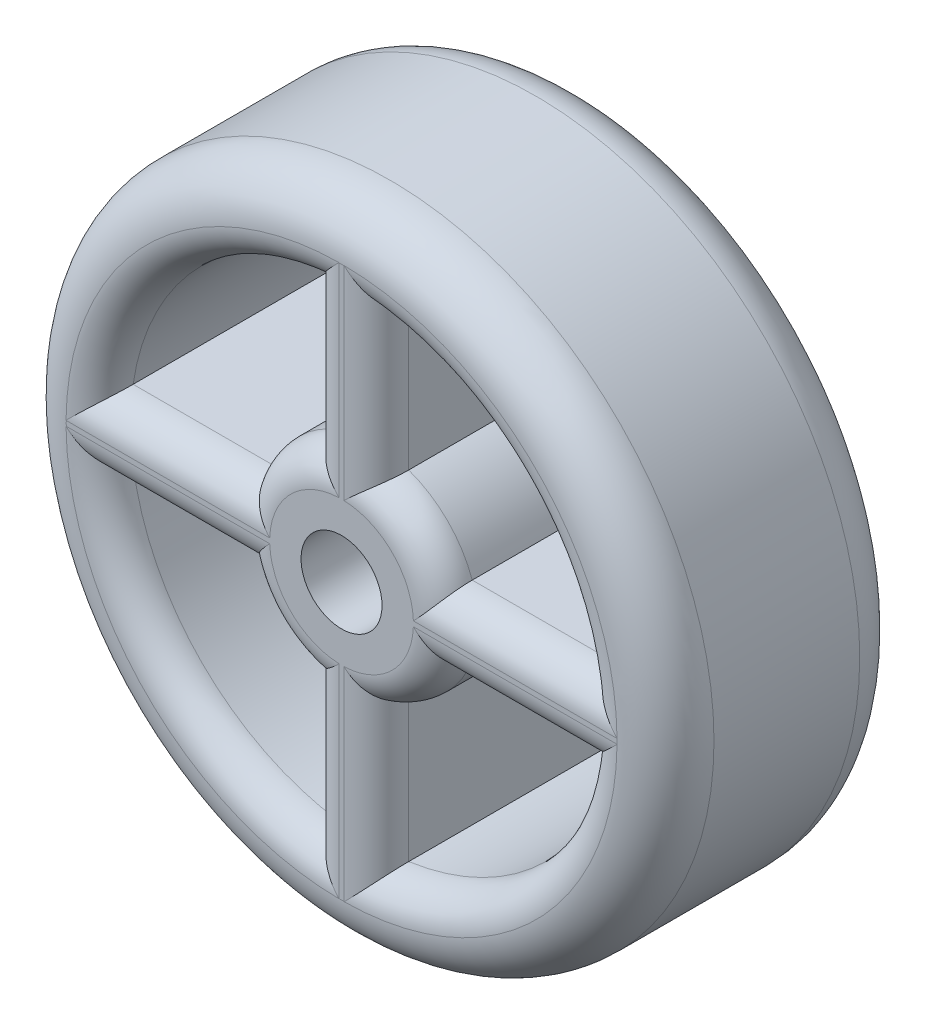
SolidWorks part; units mm, degrees
ref_plane "Front Plane" through (0, 0, 0) normal (0, 0, 1) x (1, 0, 0)
ref_plane "Top Plane" through (0, 0, 0) normal (0, 1, 0) x (1, 0, 0)
ref_plane "Right Plane" through (0, 0, 0) normal (1, 0, 0) x (0, 0, -1)
sketch "Sketch2" plane through (0, 0, 0) normal (0, 0, 1) x (1, 0, 0)
  line L12 (-2.1463, 6.0707) -> (-2.1463, 14.8701)
  line L13 (2.1463, 6.0707) -> (2.1463, 14.8701)
  line L14 (6.0707, 2.1463) -> (14.8701, 2.1463)
  line L16 (6.0647, -2.1631) -> (14.8676, -2.1631)
  line L17 (2.1463, -6.0707) -> (2.1463, -14.8701)
  line L19 (-2.1463, -6.0707) -> (-2.1463, -14.8701)
  line L20 (-6.0647, -2.1631) -> (-14.8676, -2.1631)
  line L22 (-6.0707, 2.1463) -> (-14.8701, 2.1463)
  circle A2 centre (0, 0) radius 2.5
  arc A3 (-2.1463, 6.0707) -> (-6.0707, 2.1463) centre (0, 0) ccw
  arc A4 (-2.1463, 14.8701) -> (-14.8701, 2.1463) centre (0, 0) ccw
  circle A5 centre (0, 0) radius 7.5
  circle A6 centre (0, 0) radius 20
  arc A7 (-6.0647, -2.1631) -> (-2.1463, -6.0707) centre (0, 0) ccw
  arc A8 (6.0707, 2.1463) -> (2.1463, 6.0707) centre (0, 0) ccw
  arc A9 (-14.8676, -2.1631) -> (-2.1463, -14.8701) centre (0, 0) ccw
  arc A10 (2.1463, -6.0707) -> (6.0647, -2.1631) centre (0, 0) ccw
  arc A11 (2.1463, -14.8701) -> (14.8676, -2.1631) centre (0, 0) ccw
  arc A12 (14.8701, 2.1463) -> (2.1463, 14.8701) centre (0, 0) ccw
  dimension "D1" = 5
  dimension "D2" = 40
  dimension "D3" = 15
extrude "Boss-Extrude1" add sketch "Sketch2" along normal blind 15 contours A6 A5 | A5 A12 L14 A8 L13 A11 L17 A10 L16 A9 L20 A7 L19 A2 A4 L12 A3 L22 region at (-1.9342, 6.6285, 0) region at (-19.4343, 0, 0)
sketch "Sketch3" plane through (0, 0, 15) normal (0, 0, 1) x (1, 0, 0)
  circle A0 centre (0, 0) radius 2.4167
extrude "Boss-Extrude2" add sketch "Sketch3" against normal blind 15 separate body
fillet "Fillet2" radius 2 16 edges at (-10.4704, 2.1463, 15) (-4.553, 4.553, 15) (-2.1463, 10.4704, 15) (-10.6237, 10.6237, 15) (-2.1463, -10.4704, 15) (-4.5467, -4.5593, 15) (-10.4662, -2.1631, 15) (-10.6177, -10.6297, 15) (2.1463, 10.4704, 15) (4.553, 4.553, 15) (10.4704, 2.1463, 15) (10.6237, 10.6237, 15) (10.4662, -2.1631, 15) (4.5467, -4.5593, 15) (2.1463, -10.4704, 15) (10.6177, -10.6297, 15)
fillet "Fillet3" radius 3 2 edges at (20, 0, 15) (20, 0, 0)
sketch "Sketch4" plane through (0, 0, 15) normal (0, 0, 1) x (1, 0, 0)
  circle A0 centre (0, 0) radius 2.4681
extrude "Cut-Extrude1" cut sketch "Sketch4" against normal blind 7.5
